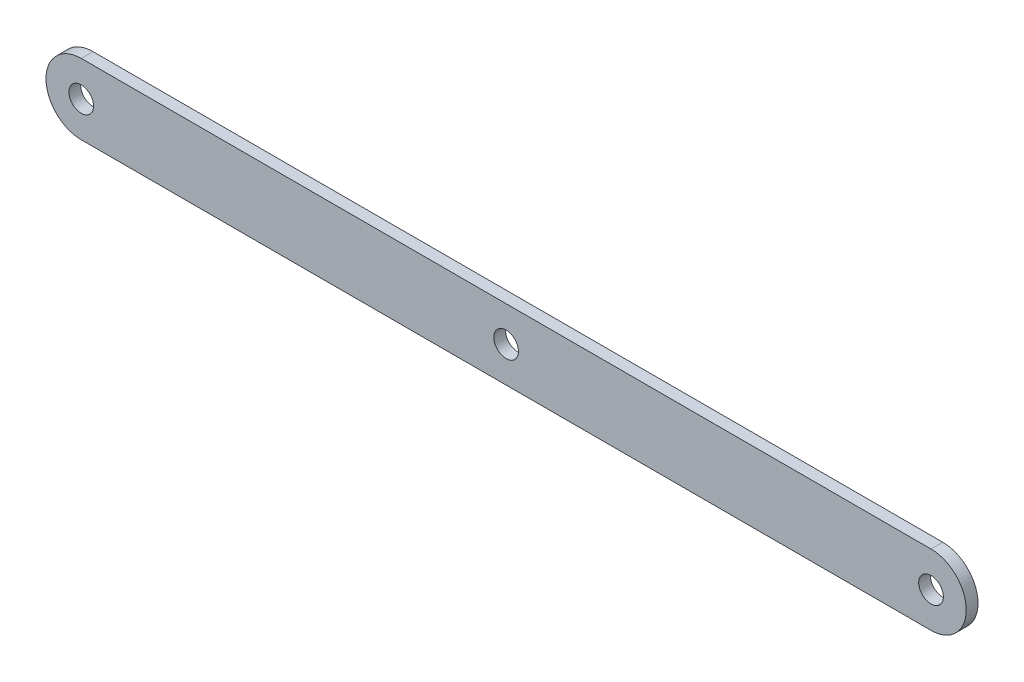
SolidWorks part; units mm, degrees
ref_plane "Vorne" through (0, 0, 0) normal (0, 0, 1) x (1, 0, 0)
ref_plane "Oben" through (0, 0, 0) normal (0, 1, 0) x (1, 0, 0)
ref_plane "Seite" through (0, 0, 0) normal (1, 0, 0) x (0, 0, -1)
sketch "Skizze2" plane through (0, 0, 0) normal (0, 0, 1) x (1, 0, 0)
  line L0 (50, 0) -> (-50, 0) construction
  line L1 (-72.34, 6) -> (72.34, 6)
  line L2 (-72.34, -6) -> (72.34, -6)
  line L3 (0, 6) -> (0, -6) construction
  arc A0 (-72.34, 6) -> (-72.34, -6) centre (-72.34, 0) ccw
  arc A1 (72.34, -6) -> (72.34, 6) centre (72.34, 0) ccw
  circle A2 centre (-72.34, 0) radius 2.1
  circle A3 centre (72.34, 0) radius 2.1
  circle A4 centre (0, 0) radius 2.1
  dimension "D1" = 4.2
  dimension "D2" = 144.68
  dimension "D3" = 12
extrude "Aufsatz-Linear austragen1" add sketch "Skizze2" along normal blind 2
